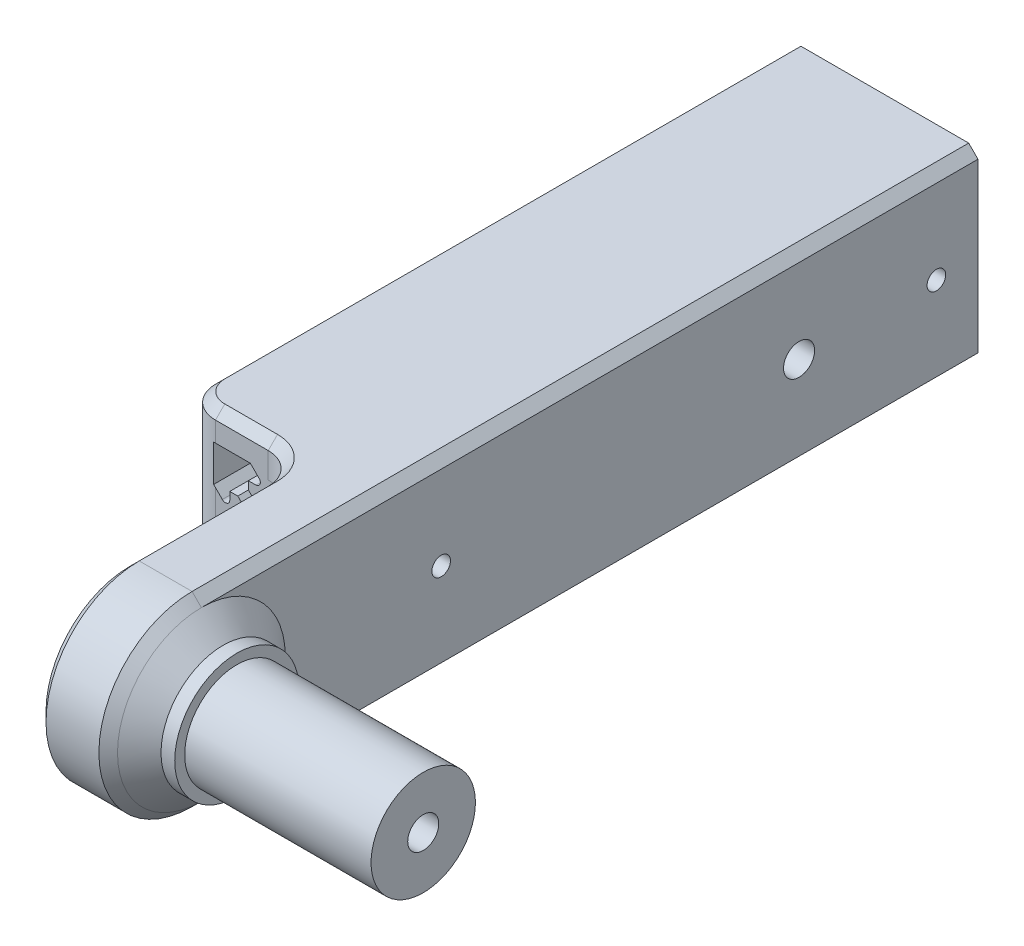
SolidWorks part; units mm, degrees
ref_plane "Front Plane" through (0, 0, 0) normal (0, 0, 1) x (1, 0, 0)
ref_plane "Top Plane" through (0, 0, 0) normal (0, 1, 0) x (1, 0, 0)
ref_plane "Right Plane" through (0, 0, 0) normal (1, 0, 0) x (0, 0, -1)
sketch "Sketch1" plane through (0, 0, 0) normal (0, 0, 1) x (1, 0, 0)
  line L0 (17.8029, 19.5) -> (12.1971, 19.5)
  line L1 (0, 0) -> (30, 0)
  line L2 (0, 0) -> (0, 30)
  line L3 (0, 30) -> (30, 30)
  line L4 (30, 0) -> (30, 30)
  line L5 (12.1971, 19.5) -> (10.2899, 21.4071)
  line L6 (10.2899, 21.4071) -> (10.2899, 22.7)
  line L7 (10.2899, 22.7) -> (11.5172, 22.7)
  line L8 (12.0121, 23.895) -> (10.6121, 25.295)
  line L9 (4.705, 19.3879) -> (6.105, 17.9879)
  line L10 (7.3, 18.4828) -> (7.3, 19.7101)
  line L11 (7.3, 19.7101) -> (8.5929, 19.7101)
  line L12 (8.5929, 19.7101) -> (10.5, 17.8029)
  line L13 (10.5, 17.8029) -> (10.5, 12.1971)
  line L14 (10.5, 12.1971) -> (8.5929, 10.2899)
  line L15 (8.5929, 10.2899) -> (7.3, 10.2899)
  line L16 (7.3, 10.2899) -> (7.3, 11.5172)
  line L17 (6.105, 12.0121) -> (4.705, 10.6121)
  line L18 (10.6121, 4.705) -> (12.0121, 6.105)
  line L19 (11.5172, 7.3) -> (10.2899, 7.3)
  line L20 (10.2899, 7.3) -> (10.2899, 8.5929)
  line L21 (10.2899, 8.5929) -> (12.1971, 10.5)
  line L22 (12.1971, 10.5) -> (17.8029, 10.5)
  line L23 (10.6121, 4.705) -> (4.705, 4.705)
  line L24 (4.705, 4.705) -> (4.705, 10.6121)
  line L25 (4.705, 19.3879) -> (4.705, 25.295)
  line L26 (4.705, 25.295) -> (10.6121, 25.295)
  line L27 (15, 28.3991) -> (15, -1.6009) construction
  line L28 (25.295, 25.295) -> (19.3879, 25.295)
  line L29 (25.295, 19.3879) -> (25.295, 25.295)
  line L30 (25.295, 4.705) -> (25.295, 10.6121)
  line L31 (19.3879, 4.705) -> (25.295, 4.705)
  line L32 (19.7101, 8.5929) -> (17.8029, 10.5)
  line L33 (19.7101, 7.3) -> (19.7101, 8.5929)
  line L34 (18.4828, 7.3) -> (19.7101, 7.3)
  line L35 (19.3879, 4.705) -> (17.9879, 6.105)
  line L36 (23.895, 12.0121) -> (25.295, 10.6121)
  line L37 (22.7, 10.2899) -> (22.7, 11.5172)
  line L38 (21.4071, 10.2899) -> (22.7, 10.2899)
  line L39 (19.5, 12.1971) -> (21.4071, 10.2899)
  line L40 (19.5, 17.8029) -> (19.5, 12.1971)
  line L41 (21.4071, 19.7101) -> (19.5, 17.8029)
  line L42 (22.7, 19.7101) -> (21.4071, 19.7101)
  line L43 (22.7, 18.4828) -> (22.7, 19.7101)
  line L44 (25.295, 19.3879) -> (23.895, 17.9879)
  line L45 (17.9879, 23.895) -> (19.3879, 25.295)
  line L46 (19.7101, 22.7) -> (18.4828, 22.7)
  line L47 (19.7101, 21.4071) -> (19.7101, 22.7)
  line L48 (17.8029, 19.5) -> (19.7101, 21.4071)
  line L49 (10.5, 15) -> (19.5, 15) construction
  arc A1 (17.9879, 6.105) -> (18.4828, 7.3) centre (18.4828, 6.6) cw
  arc A2 (11.5172, 22.7) -> (12.0121, 23.895) centre (11.5172, 23.4) ccw
  arc A3 (22.7, 11.5172) -> (23.895, 12.0121) centre (23.4, 11.5172) cw
  arc A4 (23.895, 17.9879) -> (22.7, 18.4828) centre (23.4, 18.4828) cw
  arc A5 (6.105, 17.9879) -> (7.3, 18.4828) centre (6.6, 18.4828) ccw
  arc A6 (7.3, 11.5172) -> (6.105, 12.0121) centre (6.6, 11.5172) ccw
  arc A7 (18.4828, 22.7) -> (17.9879, 23.895) centre (18.4828, 23.4) cw
  arc A8 (12.0121, 6.105) -> (11.5172, 7.3) centre (11.5172, 6.6) ccw
  point P69 (19.5, 15)
  point P70 (15, 30)
  point P73 (30, 15)
  dimension "D1" = 30
  dimension "D9" = 0.7
  dimension "D18" = 0.7
  dimension "D33" = 0.7
  dimension "D2" = 30
  dimension "D3" = 5.6059
  dimension "D4" = 2.6971
  dimension "D5" = 1.2929
  dimension "D6" = 2.595
  dimension "D7" = 135
  dimension "D8" = 1.2934
  dimension "D10" = 1.9799
  dimension "D11" = 135
  dimension "D12" = 1.2272
  dimension "D13" = 5.6059
  dimension "D14" = 2.6971
  dimension "D15" = 1.2929
  dimension "D16" = 1.2272
  dimension "D17" = 1.2934
  dimension "D19" = 1.9799
  dimension "D20" = 225
  dimension "D21" = 5.9071
  dimension "D22" = 135
  dimension "D23" = 90
  dimension "D24" = 135
  dimension "D25" = 2.595
  dimension "D26" = 135
  dimension "D27" = 135
  dimension "D28" = 1.2934
  dimension "D29" = 5.9071
  dimension "D30" = 1.9799
  dimension "D31" = 135
  dimension "D32" = 1.2934
  dimension "D34" = 1.2272
  dimension "D35" = 90
  dimension "D36" = 135
  dimension "D37" = 1.2929
  dimension "D38" = 2.595
  dimension "D39" = 2.6971
  dimension "D40" = 5.6059
  dimension "D41" = 5.9071
extrude "Boss-Extrude3" add sketch "Sketch1" along normal blind 95
sketch "Sketch3" plane through (30, 0, 0) normal (1, 0, 0) x (0, 0, -1)
  line L1 (-95, 0) -> (-95, 30) construction
  line L2 (-125, 30) -> (-95, 30)
  line L3 (-125, 0) -> (-95, 0)
  line L8 (0, 0) -> (0, 30)
  line L9 (0, 30) -> (-95, 30)
  line L10 (-95, 30) -> (-95, 0)
  line L11 (-95, 0) -> (0, 0)
  line L14 (-95, 30) -> (-95, 0)
  arc A1 (-125, 30) -> (-125, 0) centre (-125, 15) ccw
  point P5 (-95, 15)
  dimension "D1" = 30
  dimension "D2" = 30
  dimension "D3" = 0
extrude "Boss-Extrude4" add sketch "Sketch3" against normal blind 30
sketch "Sketch4" plane through (0, 30, 0) normal (0, 1, 0) x (1, 0, 0)
  line L2 (0, -140) -> (30, -140) construction
  line L3 (5, -97.7296) -> (13.4906, -97.7296)
  line L5 (0, -140) -> (18.4906, -140)
  line L6 (18.4906, -102.7296) -> (18.4906, -140)
  line L7 (0, -92.7296) -> (0, -140)
  line L9 (0, -125) -> (0, 0) construction
  arc A1 (13.4906, -97.7296) -> (18.4906, -102.7296) centre (13.4906, -102.7296) cw
  arc A2 (5, -97.7296) -> (0, -92.7296) centre (5, -92.7296) cw
  point P16 (0, -125)
  dimension "D1" = 5
  dimension "D2" = 5
extrude "Cut-Extrude1" cut sketch "Sketch4" against normal through all
sketch "Sketch5" plane through (30, 0, 0) normal (1, 0, 0) x (0, 0, -1)
  circle A0 centre (-125, 15) radius 10
  dimension "D1" = 20
extrude "Boss-Extrude5" add sketch "Sketch5" along normal blind 5.71
sketch "Sketch6" plane through (35.71, 0, 0) normal (1, 0, 0) x (0, 0, -1)
  circle A0 centre (-125, 15) radius 8.4
  dimension "D1" = 16.8
extrude "Boss-Extrude6" add sketch "Sketch6" along normal blind 30
sketch "Sketch8" plane through (0, 0, 0) normal (-1, 0, 0) x (0, 0, 1)
  line L0 (0, 30) -> (0, 0) construction
  circle A0 centre (6.7, 15) radius 1.5
  circle A1 centre (86.4, 15) radius 1.5
  circle A2 centre (28.8, 15) radius 2.5
  circle A3 centre (125, 15) radius 2.5
  point P8 (0, 15)
  dimension "D1" = 5
  dimension "D2" = 3
  dimension "D3" = 3
  dimension "D7" = 5
  dimension "D4" = 6.7
  dimension "D5" = 22.1
  dimension "D6" = 57.6
extrude "Cut-Extrude2" cut sketch "Sketch8" against normal through all
chamfer "Chamfer1" distance 1.5 angle 45 14 edges at (30, 0, 62.5) (0, 0, 46.3648) (0, 30, 46.3648) (30, 30, 62.5) (9.2453, 0, 97.7296) (1.4645, 0, 96.2651) (9.2453, 30, 97.7296) (1.4645, 30, 96.2651) (17.0262, 0, 99.1941) (18.4906, 0, 113.8648) (18.4906, 15, 140) (18.4906, 30, 113.8648) (17.0262, 30, 99.1941) (30, 15, 140)
chamfer "Chamfer2" distance 3.5 angle 45 1 edges at (30, 15, 135)
sketch "Sketch9" plane through (0, 0, 95) normal (0, 0, -1) x (-1, 0, 0)
  line L44 (-10.6121, 4.705) -> (-4.705, 4.705)
  line L45 (-4.705, 4.705) -> (-4.705, 10.6121)
  line L46 (-4.705, 10.6121) -> (-6.105, 12.0121)
  line L47 (-7.3, 11.5172) -> (-7.3, 10.2899)
  line L48 (-7.3, 10.2899) -> (-8.5929, 10.2899)
  line L49 (-8.5929, 10.2899) -> (-10.5, 12.1971)
  line L50 (-10.5, 12.1971) -> (-10.5, 17.8029)
  line L51 (-10.5, 17.8029) -> (-8.5929, 19.7101)
  line L52 (-8.5929, 19.7101) -> (-7.3, 19.7101)
  line L53 (-7.3, 19.7101) -> (-7.3, 18.4828)
  line L54 (-6.105, 17.9879) -> (-4.705, 19.3879)
  line L55 (-4.705, 19.3879) -> (-4.705, 25.295)
  line L56 (-4.705, 25.295) -> (-10.6121, 25.295)
  line L57 (-10.6121, 25.295) -> (-12.0121, 23.895)
  line L58 (-11.5172, 22.7) -> (-10.2899, 22.7)
  line L59 (-10.2899, 22.7) -> (-10.2899, 21.4071)
  line L60 (-10.2899, 21.4071) -> (-12.1971, 19.5)
  line L61 (-12.1971, 19.5) -> (-17.8029, 19.5)
  line L62 (-17.8029, 19.5) -> (-19.7101, 21.4071)
  line L63 (-19.7101, 21.4071) -> (-19.7101, 22.7)
  line L64 (-19.7101, 22.7) -> (-18.4828, 22.7)
  line L65 (-17.9879, 23.895) -> (-19.3879, 25.295)
  line L66 (-19.3879, 25.295) -> (-25.295, 25.295)
  line L67 (-25.295, 25.295) -> (-25.295, 19.3879)
  line L68 (-25.295, 19.3879) -> (-23.895, 17.9879)
  line L69 (-22.7, 18.4828) -> (-22.7, 19.7101)
  line L70 (-22.7, 19.7101) -> (-21.4071, 19.7101)
  line L71 (-21.4071, 19.7101) -> (-19.5, 17.8029)
  line L72 (-19.5, 17.8029) -> (-19.5, 12.1971)
  line L73 (-19.5, 12.1971) -> (-21.4071, 10.2899)
  line L74 (-21.4071, 10.2899) -> (-22.7, 10.2899)
  line L75 (-22.7, 10.2899) -> (-22.7, 11.5172)
  line L76 (-23.895, 12.0121) -> (-25.295, 10.6121)
  line L77 (-25.295, 10.6121) -> (-25.295, 4.705)
  line L78 (-25.295, 4.705) -> (-19.3879, 4.705)
  line L79 (-19.3879, 4.705) -> (-17.9879, 6.105)
  line L80 (-18.4828, 7.3) -> (-19.7101, 7.3)
  line L81 (-19.7101, 7.3) -> (-19.7101, 8.5929)
  line L82 (-19.7101, 8.5929) -> (-17.8029, 10.5)
  line L83 (-17.8029, 10.5) -> (-12.1971, 10.5)
  line L84 (-12.1971, 10.5) -> (-10.2899, 8.5929)
  line L85 (-10.2899, 8.5929) -> (-10.2899, 7.3)
  line L86 (-10.2899, 7.3) -> (-11.5172, 7.3)
  line L87 (-12.0121, 6.105) -> (-10.6121, 4.705)
  line L88 (-10.6121, 4.705) -> (-4.705, 4.705)
  line L89 (-4.705, 4.705) -> (-4.705, 10.6121)
  line L90 (-4.705, 10.6121) -> (-6.105, 12.0121)
  line L91 (-7.3, 11.5172) -> (-7.3, 10.2899)
  line L92 (-7.3, 10.2899) -> (-8.5929, 10.2899)
  line L93 (-8.5929, 10.2899) -> (-10.5, 12.1971)
  line L94 (-10.5, 12.1971) -> (-10.5, 17.8029)
  line L95 (-10.5, 17.8029) -> (-8.5929, 19.7101)
  line L96 (-8.5929, 19.7101) -> (-7.3, 19.7101)
  line L97 (-7.3, 19.7101) -> (-7.3, 18.4828)
  line L98 (-6.105, 17.9879) -> (-4.705, 19.3879)
  line L99 (-4.705, 19.3879) -> (-4.705, 25.295)
  line L100 (-4.705, 25.295) -> (-10.6121, 25.295)
  line L101 (-10.6121, 25.295) -> (-12.0121, 23.895)
  line L102 (-11.5172, 22.7) -> (-10.2899, 22.7)
  line L103 (-10.2899, 22.7) -> (-10.2899, 21.4071)
  line L104 (-10.2899, 21.4071) -> (-12.1971, 19.5)
  line L105 (-12.1971, 19.5) -> (-17.8029, 19.5)
  line L106 (-17.8029, 19.5) -> (-19.7101, 21.4071)
  line L107 (-19.7101, 21.4071) -> (-19.7101, 22.7)
  line L108 (-19.7101, 22.7) -> (-18.4828, 22.7)
  line L109 (-17.9879, 23.895) -> (-19.3879, 25.295)
  line L110 (-19.3879, 25.295) -> (-25.295, 25.295)
  line L111 (-25.295, 25.295) -> (-25.295, 19.3879)
  line L112 (-25.295, 19.3879) -> (-23.895, 17.9879)
  line L113 (-22.7, 18.4828) -> (-22.7, 19.7101)
  line L114 (-22.7, 19.7101) -> (-21.4071, 19.7101)
  line L115 (-21.4071, 19.7101) -> (-19.5, 17.8029)
  line L116 (-19.5, 17.8029) -> (-19.5, 12.1971)
  line L117 (-19.5, 12.1971) -> (-21.4071, 10.2899)
  line L118 (-21.4071, 10.2899) -> (-22.7, 10.2899)
  line L119 (-22.7, 10.2899) -> (-22.7, 11.5172)
  line L120 (-23.895, 12.0121) -> (-25.295, 10.6121)
  line L121 (-25.295, 10.6121) -> (-25.295, 4.705)
  line L122 (-25.295, 4.705) -> (-19.3879, 4.705)
  line L123 (-19.3879, 4.705) -> (-17.9879, 6.105)
  line L124 (-18.4828, 7.3) -> (-19.7101, 7.3)
  line L125 (-19.7101, 7.3) -> (-19.7101, 8.5929)
  line L126 (-19.7101, 8.5929) -> (-17.8029, 10.5)
  line L127 (-17.8029, 10.5) -> (-12.1971, 10.5)
  line L128 (-12.1971, 10.5) -> (-10.2899, 8.5929)
  line L129 (-10.2899, 8.5929) -> (-10.2899, 7.3)
  line L130 (-10.2899, 7.3) -> (-11.5172, 7.3)
  line L131 (-12.0121, 6.105) -> (-10.6121, 4.705)
  arc A8 (-6.105, 12.0121) -> (-7.3, 11.5172) centre (-6.6, 11.5172) ccw
  arc A9 (-7.3, 18.4828) -> (-6.105, 17.9879) centre (-6.6, 18.4828) ccw
  arc A10 (-12.0121, 23.895) -> (-11.5172, 22.7) centre (-11.5172, 23.4) ccw
  arc A11 (-18.4828, 22.7) -> (-17.9879, 23.895) centre (-18.4828, 23.4) ccw
  arc A12 (-23.895, 17.9879) -> (-22.7, 18.4828) centre (-23.4, 18.4828) ccw
  arc A13 (-22.7, 11.5172) -> (-23.895, 12.0121) centre (-23.4, 11.5172) ccw
  arc A14 (-17.9879, 6.105) -> (-18.4828, 7.3) centre (-18.4828, 6.6) ccw
  arc A15 (-11.5172, 7.3) -> (-12.0121, 6.105) centre (-11.5172, 6.6) ccw
  arc A16 (-6.105, 12.0121) -> (-7.3, 11.5172) centre (-6.6, 11.5172) ccw
  arc A17 (-7.3, 18.4828) -> (-6.105, 17.9879) centre (-6.6, 18.4828) ccw
  arc A18 (-12.0121, 23.895) -> (-11.5172, 22.7) centre (-11.5172, 23.4) ccw
  arc A19 (-18.4828, 22.7) -> (-17.9879, 23.895) centre (-18.4828, 23.4) ccw
  arc A20 (-23.895, 17.9879) -> (-22.7, 18.4828) centre (-23.4, 18.4828) ccw
  arc A21 (-22.7, 11.5172) -> (-23.895, 12.0121) centre (-23.4, 11.5172) ccw
  arc A22 (-17.9879, 6.105) -> (-18.4828, 7.3) centre (-18.4828, 6.6) ccw
  arc A23 (-11.5172, 7.3) -> (-12.0121, 6.105) centre (-11.5172, 6.6) ccw
  dimension "D1" = 0
extrude "Cut-Extrude3" cut sketch "Sketch9" against normal blind 17
sketch "Sketch10" plane through (18.4906, 0, 0) normal (-1, 0, 0) x (0, 0, 1)
  line L1 (112, 24.3977) -> (97.7296, 24.3977)
  line L2 (112, 24.3977) -> (112, 19.5)
  line L3 (112, 19.5) -> (97.7296, 19.5)
  line L4 (97.7296, 24.3977) -> (97.7296, 19.5)
  line L5 (112, 5.6023) -> (97.7296, 5.6023)
  line L6 (112, 5.6023) -> (112, 10.5)
  line L7 (112, 10.5) -> (97.7296, 10.5)
  line L8 (97.7296, 5.6023) -> (97.7296, 10.5)
  point P12 (97.7209, 7.3)
  point P13 (97.7296, 7.3)
  point P14 (112, 24.3977)
extrude "Cut-Extrude4" cut sketch "Sketch10" against normal blind 2 and the other way blind 10
